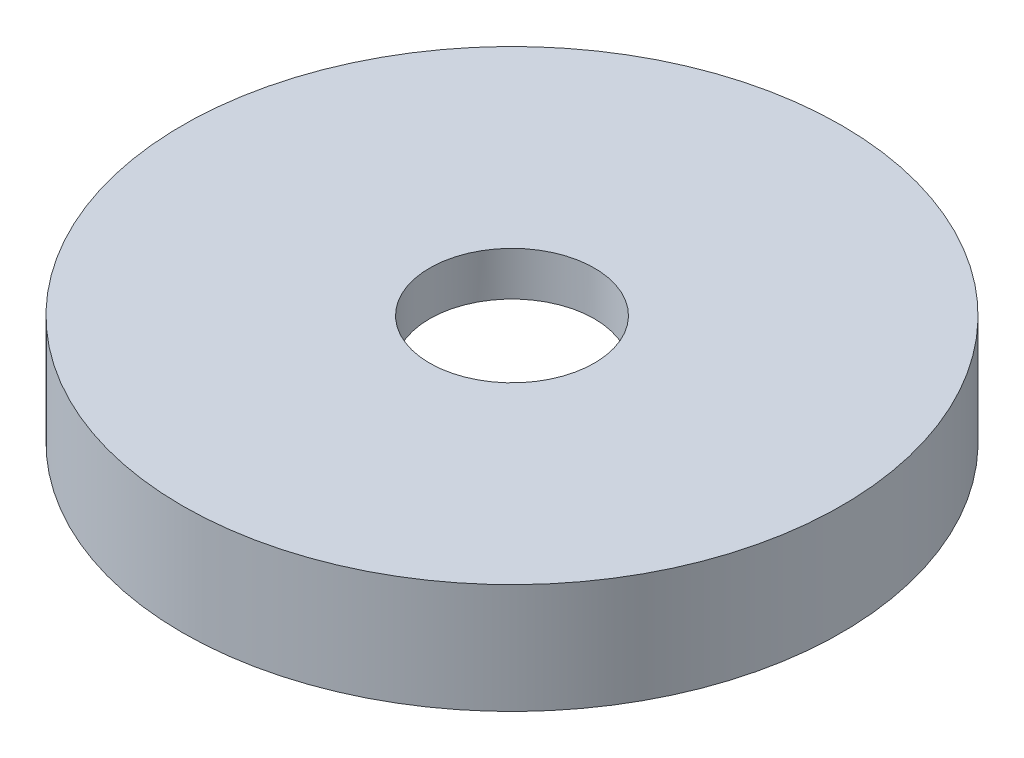
SolidWorks part; units mm, degrees
ref_plane "Plan de face" through (0, 0, 0) normal (0, 0, 1) x (1, 0, 0)
ref_plane "Plan de dessus" through (0, 0, 0) normal (0, 1, 0) x (1, 0, 0)
ref_plane "Plan de droite" through (0, 0, 0) normal (1, 0, 0) x (0, 0, -1)
sketch "Esquisse1" plane through (0, 0, 0) normal (0, 1, 0) x (1, 0, 0)
  circle A0 centre (0, 0) radius 30
  dimension "D1" = 60
extrude "Boss.-Extru.1" add sketch "Esquisse1" along normal blind 10
sketch "Esquisse2" plane through (0, 0, 0) normal (0, -1, 0) x (1, 0, 0)
  circle A0 centre (0, 0) radius 17.5
  dimension "D1" = 35
extrude "Enlèv. mat.-Extru.1" cut sketch "Esquisse2" against normal blind 6
sketch "Esquisse3" plane through (0, 10, 0) normal (0, 1, 0) x (1, 0, 0)
  circle A0 centre (0, 0) radius 7.5
  dimension "D1" = 15
extrude "Enlèv. mat.-Extru.2" cut sketch "Esquisse3" against normal through all
